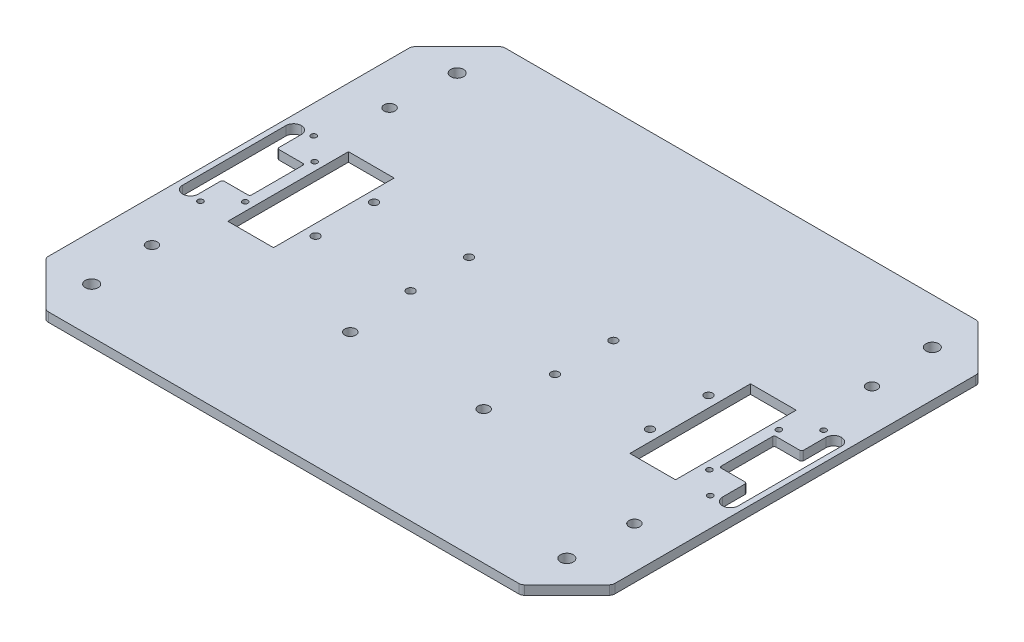
SolidWorks part; units mm, degrees
ref_plane "Plan de face" through (0, 0, 0) normal (0, 0, 1) x (1, 0, 0)
ref_plane "Plan de dessus" through (0, 0, 0) normal (0, 1, 0) x (1, 0, 0)
ref_plane "Plan de droite" through (0, 0, 0) normal (1, 0, 0) x (0, 0, -1)
sketch "Esquisse1" plane through (0, 0, 0) normal (0, 1, 0) x (1, 0, 0)
  line L0 (0, 125) -> (0, -125) construction
  line L1 (-155, 0) -> (155, 0) construction
  line L2 (-130, 125) -> (130, 125)
  line L3 (-130, -125) -> (130, -125)
  line L4 (-155, 100) -> (-155, -100)
  line L5 (155, 100) -> (155, -100)
  line L6 (-155, 100) -> (-130, 125)
  line L7 (-155, -100) -> (-130, -125)
  line L8 (130, -125) -> (155, -100)
  line L9 (130, 125) -> (155, 100)
  point P4 (0, 0)
  point P8 (0, 0)
  point P10 (0, 125)
  point P14 (0, -125)
  point P17 (-155, 0)
  point P20 (155, 0)
  dimension "D1" = 310
  dimension "D2" = 250
  dimension "D3" = 135
  dimension "D4" = 260
  dimension "D5" = 200
extrude "Boss.-Extru.1" add sketch "Esquisse1" along normal blind 5
fillet "Congé1" radius 3 8 edges at (-155, 2.5, 100) (-130, 2.5, 125) (130, 2.5, 125) (155, 2.5, 100) (155, 2.5, -100) (130, 2.5, -125) (-130, 2.5, -125) (-155, 2.5, -100)
sketch "Esquisse2" plane through (0, 5, 0) normal (0, 1, 0) x (1, 0, 0)
  line L0 (155, 0) -> (-155, 0) construction
  line L1 (-155, 98.7574) -> (-155, -98.7574) construction
  line L2 (-132, 0) -> (-132, -65) construction
  line L3 (-132, -65) -> (-155, -65) construction
  line L4 (0, 125) -> (0, -125) construction
  line L5 (-128.7574, -125) -> (128.7574, -125) construction
  circle A0 centre (-132, -65) radius 3
  circle A1 centre (-132, 65) radius 3
  circle A2 centre (132, -65) radius 3
  circle A3 centre (132, 65) radius 3
  point P6 (0, 0)
  point P18 (0, 0)
  dimension "D3" = 6
  dimension "D1" = 23
  dimension "D2" = 65
extrude "Perçage Profilé" cut sketch "Esquisse2" against normal through all
sketch "Esquisse3" plane through (0, 5, 0) normal (0, 1, 0) x (1, 0, 0)
  line L0 (-127, 19) -> (-127, -19) construction
  line L1 (155, 0) -> (-155, 0) construction
  line L2 (-155, 98.7574) -> (-155, -98.7574) construction
  line L3 (0, 125) -> (0, -125) construction
  line L4 (-128.7574, -125) -> (128.7574, -125) construction
  line L5 (-139.5, -31) -> (-139.5, 31) construction
  circle A0 centre (-127, 19) radius 1.5
  circle A1 centre (-127, -19) radius 1.5
  circle A2 centre (127, -19) radius 1.5
  circle A3 centre (127, 19) radius 1.5
  circle A4 centre (-139.5, 31) radius 1.5
  circle A5 centre (-139.5, -31) radius 1.5
  circle A6 centre (139.5, -31) radius 1.5
  circle A7 centre (139.5, 31) radius 1.5
  point P4 (-127, 0)
  point P10 (0, 0)
  point P16 (0, 0)
  point P23 (-139.5, 0)
  dimension "D2" = 3
  dimension "D1" = 38
  dimension "D3" = 28
  dimension "D4" = 62
  dimension "D5" = 12.5
extrude "Perçage Encodeur" cut sketch "Esquisse3" against normal through all
sketch "Esquisse4" plane through (0, 5, 0) normal (0, 1, 0) x (1, 0, 0)
  line L0 (155, 0) -> (-155, 0) construction
  line L1 (143.5, -15) -> (129.5, -15)
  line L2 (-128.5, -14) -> (-128.5, 14)
  line L4 (-129.5, 15) -> (-143.5, 15)
  line L5 (-143.5, 15) -> (-143.5, 32.5)
  line L6 (-143.5, 32.5) -> (-152, 32.5)
  line L7 (-152, 32.5) -> (-152, -32.5)
  line L8 (-152, -32.5) -> (-143.5, -32.5)
  line L9 (-143.5, -32.5) -> (-143.5, -15)
  line L10 (-143.5, -15) -> (-129.5, -15)
  line L12 (-143.5, 15) -> (-143.5, -15) construction
  line L13 (143.5, -32.5) -> (143.5, -15)
  line L14 (0, 125) -> (0, -125) construction
  line L15 (-128.7574, -125) -> (128.7574, -125) construction
  line L16 (152, -32.5) -> (143.5, -32.5)
  line L27 (-155, 98.7574) -> (-155, -98.7574) construction
  line L28 (152, 32.5) -> (152, -32.5)
  line L29 (143.5, 32.5) -> (152, 32.5)
  line L30 (143.5, 15) -> (143.5, 32.5)
  line L31 (129.5, 15) -> (143.5, 15)
  line L32 (128.5, -14) -> (128.5, 14)
  arc A0 (-128.5, -14) -> (-129.5, -15) centre (-129.5, -14) cw
  arc A1 (-128.5, 14) -> (-129.5, 15) centre (-129.5, 14) ccw
  arc A2 (128.5, 14) -> (129.5, 15) centre (129.5, 14) cw
  arc A3 (128.5, -14) -> (129.5, -15) centre (129.5, -14) ccw
  point P6 (0, 0)
  point P10 (-128.5, 0)
  point P19 (-143.5, 0)
  point P25 (0, 0)
  point P28 (-128.5, 15)
  point P32 (-152, 0)
  point P45 (128.5, 15)
  point P46 (128.5, 0)
  dimension "D2" = 1
  dimension "D1" = 15
  dimension "D3" = 8.5
  dimension "D4" = 65
  dimension "D5" = 30
  dimension "D6" = 3
extrude "Poche Roue Encodeuse" cut sketch "Esquisse4" against normal through all
fillet "Congé4" radius 1 4 edges at (143.5, 2.5, 15) (143.5, 2.5, -15) (-143.5, 2.5, 15) (-143.5, 2.5, -15)
fillet "Congé2" radius 4.25 4 edges at (152, 2.5, 32.5) (152, 2.5, -32.5) (-152, 2.5, 32.5) (-152, 2.5, -32.5)
fillet "Congé3" radius 4.25 4 edges at (143.5, 2.5, 32.5) (143.5, 2.5, -32.5) (-143.5, 2.5, 32.5) (-143.5, 2.5, -32.5)
sketch "Esquisse5" plane through (0, 5, 0) normal (0, 1, 0) x (1, 0, 0)
  line L0 (0, 125) -> (0, -125) construction
  line L1 (128.7574, 125) -> (-128.7574, 125) construction
  line L2 (-128.7574, -125) -> (128.7574, -125) construction
  line L3 (-155, 0) -> (155, 0) construction
  line L4 (-155, 98.7574) -> (-155, -98.7574) construction
  line L5 (155, -98.7574) -> (155, 98.7574) construction
  line L7 (-39.5, 16) -> (-91.5, 16) construction
  line L8 (-39.5, 16) -> (-39.5, -16) construction
  line L9 (-39.5, -16) -> (-91.5, -16) construction
  line L10 (-91.5, 16) -> (-91.5, -16) construction
  circle A0 centre (-91.5, 16) radius 2.2
  circle A1 centre (-91.5, -16) radius 2.2
  circle A2 centre (-39.5, -16) radius 2.2
  circle A3 centre (-39.5, 16) radius 2.2
  circle A4 centre (39.5, 16) radius 2.2
  circle A5 centre (39.5, -16) radius 2.2
  circle A6 centre (91.5, -16) radius 2.2
  circle A7 centre (91.5, 16) radius 2.2
  point P16 (-39.5, 0)
  dimension "D4" = 4.4
  dimension "D1" = 32
  dimension "D2" = 52
  dimension "D3" = 91.5
extrude "Perçage Bloc Moteur" cut sketch "Esquisse5" against normal through all
sketch "Esquisse6" plane through (0, 5, 0) normal (0, 1, 0) x (1, 0, 0)
  line L0 (-91.5, 16) -> (-91.5, -16) construction
  line L1 (-122.5, 33) -> (-97.5, 33)
  line L2 (-122.5, 33) -> (-122.5, -33)
  line L3 (-122.5, -33) -> (-97.5, -33)
  line L4 (-97.5, 33) -> (-97.5, -33)
  line L5 (-97.5, 0) -> (-91.5, 0) construction
  line L6 (0, 125) -> (0, -125) construction
  line L7 (-128.7574, -125) -> (128.7574, -125) construction
  line L8 (122.5, -33) -> (97.5, -33)
  line L9 (97.5, 33) -> (97.5, -33)
  line L10 (122.5, 33) -> (122.5, -33)
  line L11 (122.5, 33) -> (97.5, 33)
  point P16 (0, 0)
  dimension "D1" = 25
  dimension "D2" = 6
  dimension "D3" = 66
extrude "Poche Roue Motrice" cut sketch "Esquisse6" against normal through all
sketch "Esquisse7" plane through (0, 5, 0) normal (0, 1, 0) x (1, 0, 0)
  line L0 (-155, 98.7574) -> (-155, -98.7574) construction
  line L1 (128.7574, 125) -> (-128.7574, 125) construction
  line L2 (0, 125) -> (0, -125) construction
  line L3 (-128.7574, -125) -> (128.7574, -125) construction
  line L4 (-155, 0) -> (155, 0) construction
  line L5 (155, -98.7574) -> (155, 98.7574) construction
  circle A0 centre (-130, 100) radius 3.5
  circle A1 centre (-130, -100) radius 3.5
  circle A2 centre (130, -100) radius 3.5
  circle A3 centre (130, 100) radius 3.5
  point P12 (0, 0)
  point P18 (0, 0)
  dimension "D1" = 7
  dimension "D2" = 25
  dimension "D3" = 25
extrude "Perçage Patin" cut sketch "Esquisse7" against normal through all
sketch "Esquisse8" plane through (0, 5, 0) normal (0, 1, 0) x (1, 0, 0)
  line L0 (0, -125) -> (0, -52) construction
  line L1 (-128.7574, -125) -> (128.7574, -125) construction
  line L2 (36.5, -52) -> (-36.5, -52) construction
  circle A0 centre (-36.5, -52) radius 3
  circle A1 centre (36.5, -52) radius 3
  point P8 (0, -52)
  dimension "D3" = 6
  dimension "D1" = 73
  dimension "D2" = 73
extrude "Enlèv. mat.-Extru.1" cut sketch "Esquisse8" against normal through all
